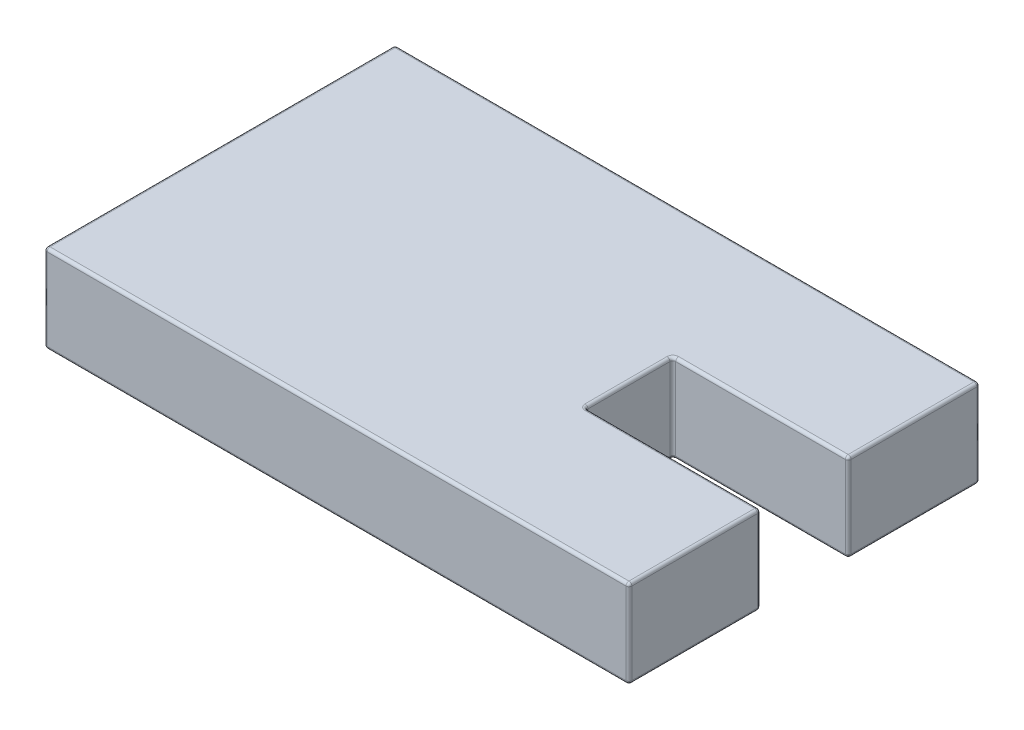
SolidWorks part; units mm, degrees
material "PTFE (general)"
ref_plane "Front Plane" through (0, 0, 0) normal (0, 0, 1) x (1, 0, 0)
ref_plane "Top Plane" through (0, 0, 0) normal (0, 1, 0) x (1, 0, 0)
ref_plane "Right Plane" through (0, 0, 0) normal (1, 0, 0) x (0, 0, -1)
sketch "Sketch1" plane through (0, 0, 0) normal (0, 0, 1) x (1, 0, 0)
  line L1 (-100, 15) -> (100, 15)
  line L2 (-100, 15) -> (-100, -15)
  line L3 (-100, -15) -> (100, -15)
  line L4 (100, 15) -> (100, -15)
  line L5 (-100, 15) -> (100, -15) construction
  line L6 (-100, -15) -> (100, 15) construction
  point P0 (0, 0)
  dimension "D1" = 200
  dimension "D2" = 30
extrude "Boss-Extrude1" add sketch "Sketch1" along normal mid plane 120
sketch "Sketch2" plane through (0, 15, 0) normal (0, 1, 0) x (1, 0, 0)
  line L0 (100, 15) -> (40, 15)
  line L1 (100, -60) -> (100, 60) construction
  line L2 (40, 15) -> (40, -15)
  line L3 (31.9251, 0) -> (10.8039, 0) construction
  line L4 (100, -15) -> (40, -15)
  line L5 (100, 15) -> (100, -15)
  point P10 (40, 0)
  dimension "D1" = 60
  dimension "D2" = 15
extrude "Cut-Extrude2" cut sketch "Sketch2" against normal through all
sketch "Sketch3" plane through (0, 0, 60) normal (0, 0, 1) x (1, 0, 0)
  line L0 (-100, 15) -> (-100, -15) construction
  line L1 (100, 15) -> (-100, 15) construction
  point P0 (-85, 0)
  dimension "D1" = 15
  dimension "D2" = 15
sketch "Sketch4" plane through (0, 0, -60) normal (0, 0, -1) x (-1, 0, 0)
  point P0 (85, 0)
ref_axis "rear-axis" through (-85, 0, 60) along (0, 0, -1)
sketch "Sketch5" plane through (0, 0, -15) normal (0, 0, 1) x (1, 0, 0)
  line L0 (100, 15) -> (-100, 15) construction
  line L1 (100, -15) -> (100, 15) construction
  point P0 (70, 0)
  dimension "D1" = 15
  dimension "D2" = 30
sketch "Sketch6" plane through (0, 0, 15) normal (0, 0, -1) x (-1, 0, 0)
  point P0 (-70, 0)
ref_axis "front-axis" through (70, 0, -15) along (0, 0, 1)
fillet "Fillet1" radius 1 24 edges at (70, -15, -15) (100, -15, -37.5) (100, 0, -15) (70, 15, -15) (40, 0, -15) (40, -15, 0) (0, -15, -60) (100, 0, -60) (100, 15, -37.5) (40, 15, 0) (40, 0, 15) (70, -15, 15) (-100, -15, 0) (-100, 0, -60) (0, 15, -60) (100, 0, 15) (70, 15, 15) (100, -15, 37.5) (0, -15, 60) (-100, 0, 60) (-100, 15, 0) (100, 15, 37.5) (100, 0, 60) (0, 15, 60)
